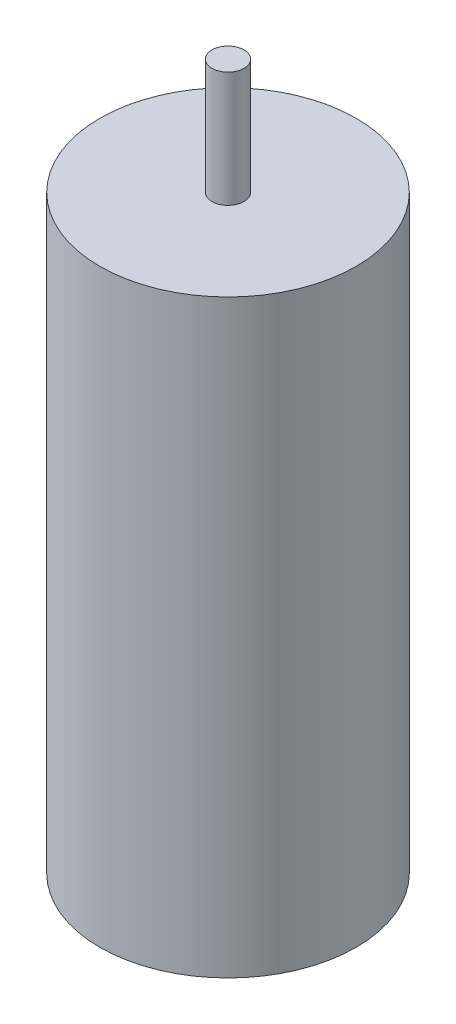
SolidWorks part; units mm, degrees
ref_plane "Front Plane" through (0, 0, 0) normal (0, 0, 1) x (1, 0, 0)
ref_plane "Top Plane" through (0, 0, 0) normal (0, 1, 0) x (1, 0, 0)
ref_plane "Right Plane" through (0, 0, 0) normal (1, 0, 0) x (0, 0, -1)
sketch "Sketch4" plane through (0, 0, 0) normal (0, 0, 1) x (1, 0, 0)
  line L0 (0, 88.1063) -> (0, -47.5917) construction
  line L1 (0, -40.3847) -> (20, -40.3847)
  line L2 (20, -40.3847) -> (20, 51.6153)
  line L3 (20, 51.6153) -> (2.5, 51.6153)
  line L4 (2.5, 51.6153) -> (2.5, 69.6153)
  line L5 (2.5, 69.6153) -> (0, 69.6153)
  line L6 (0, -40.3847) -> (0, 69.6153)
  dimension "D1" = 20
  dimension "D2" = 20
  dimension "D3" = 2.5
revolve "Revolve1" add sketch "Sketch4" angle 360 about L0
